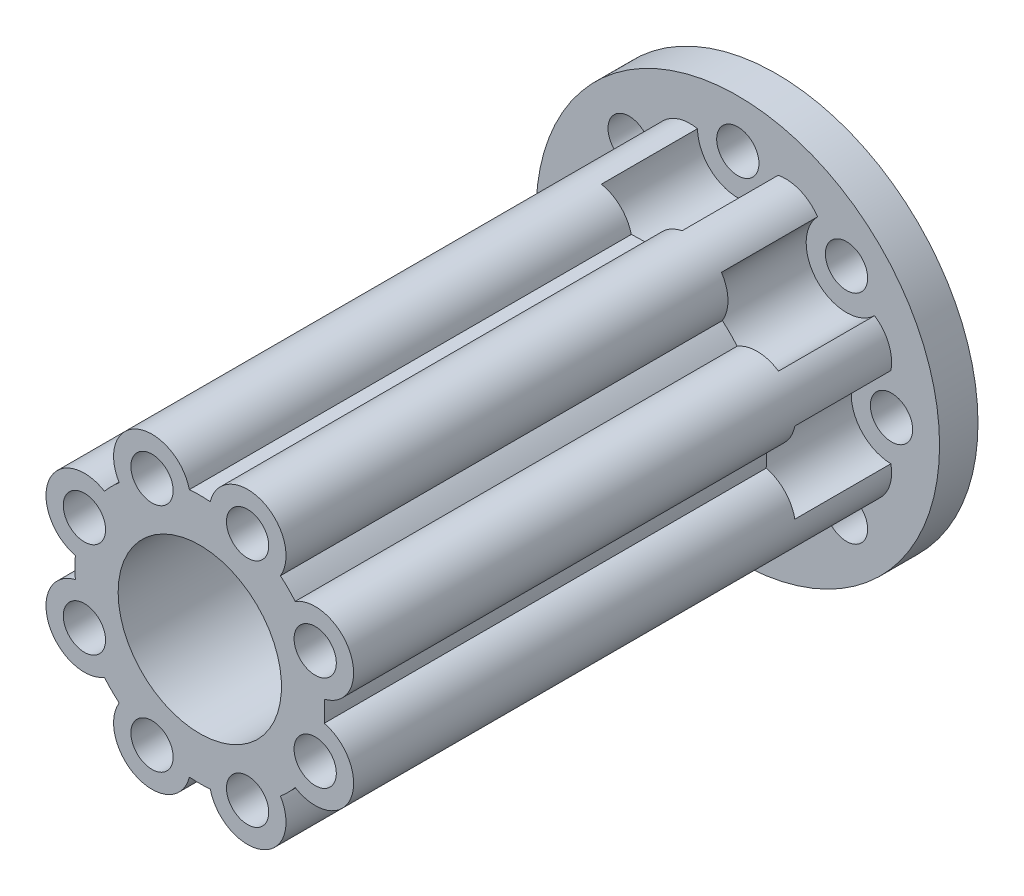
SolidWorks part; units mm, degrees
ref_plane "Alzado" through (0, 0, 0) normal (0, 0, 1) x (1, 0, 0)
ref_plane "Planta" through (0, 0, 0) normal (0, 1, 0) x (1, 0, 0)
ref_plane "Vista lateral" through (0, 0, 0) normal (1, 0, 0) x (0, 0, -1)
sketch "Croquis1" plane through (0, 0, 0) normal (0, 0, 1) x (1, 0, 0)
  circle A0 centre (0, 0) radius 10.5
  circle A1 centre (0, 0) radius 4.25
  dimension "D1" = 21
  dimension "D2" = 8.5
extrude "Saliente-Extruir1" add sketch "Croquis1" along normal blind 2
sketch "Croquis2" plane through (0, 0, 2) normal (0, 0, 1) x (1, 0, 0)
  arc A0 (-6.4347, 4.879) -> (-4.879, 6.4347) centre (-5.6569, 5.6569) ccw construction
  arc A1 (-8, -1.1) -> (-8, 1.1) centre (-8, 0) ccw construction
  arc A2 (-4.879, -6.4347) -> (-6.4347, -4.879) centre (-5.6569, -5.6569) ccw construction
  arc A3 (1.1, -8) -> (-1.1, -8) centre (0, -8) ccw construction
  arc A4 (6.4347, -4.879) -> (4.879, -6.4347) centre (5.6569, -5.6569) ccw construction
  arc A5 (8, 1.1) -> (8, -1.1) centre (8, 0) ccw construction
  arc A6 (4.879, 6.4347) -> (6.4347, 4.879) centre (5.6569, 5.6569) ccw construction
  arc A7 (-1.1, 8) -> (1.1, 8) centre (0, 8) ccw construction
  circle A8 centre (-5.6569, 5.6569) radius 1.1
  circle A9 centre (-8, 0) radius 1.1
  circle A10 centre (-5.6569, -5.6569) radius 1.1
  circle A11 centre (0, -8) radius 1.1
  circle A12 centre (5.6569, -5.6569) radius 1.1
  circle A13 centre (8, 0) radius 1.1
  circle A14 centre (5.6569, 5.6569) radius 1.1
  circle A15 centre (0, 8) radius 1.1
extrude "Cortar-Extruir1" cut sketch "Croquis2" against normal up to next
sketch "Croquis3" plane through (0, 0, 2) normal (0, 0, 1) x (1, 0, 0)
  circle A0 centre (0, 0) radius 4.25
  circle A1 centre (0, 0) radius 6.5
  dimension "D1" = 8.5
  dimension "D2" = 13
extrude "Saliente-Extruir2" add sketch "Croquis3" along normal up to surface (28 mm away)
sketch "Croquis4" plane through (0, 0, 30) normal (0, 0, 1) x (1, 0, 0)
  circle A1 centre (-2.4874, 6.0052) radius 2
  circle A2 centre (2.4874, 6.0052) radius 2
  circle A3 centre (6.0052, 2.4874) radius 2
  circle A4 centre (6.0052, -2.4874) radius 2
  circle A5 centre (2.4874, -6.0052) radius 2
  circle A6 centre (-2.4874, -6.0052) radius 2
  circle A7 centre (-6.0052, -2.4874) radius 2
  circle A8 centre (-6.0052, 2.4874) radius 2
  point P29 (0, 0)
  dimension "D1" = 4
  dimension "D3" = 6.0052
  dimension "D4" = 4.9749
  dimension "D2" = 8
extrude "Saliente-Extruir3" add sketch "Croquis4" against normal up to surface (28 mm away) up to face at (10.5, 0, 2)
sketch "Croquis6" plane through (0, 0, 2) normal (0, 0, 1) x (1, 0, 0)
  circle A0 centre (-5.6569, -5.6569) radius 1.1 construction
  circle A1 centre (0, -8) radius 1.1 construction
  circle A2 centre (5.6569, -5.6569) radius 1.1 construction
  circle A3 centre (8, 0) radius 1.1 construction
  circle A4 centre (5.6569, 5.6569) radius 1.1 construction
  circle A5 centre (0, 8) radius 1.1 construction
  circle A6 centre (-5.6569, 5.6569) radius 1.1 construction
  circle A7 centre (-8, 0) radius 1.1 construction
  circle A8 centre (-5.6569, -5.6569) radius 1.1 construction
  circle A9 centre (0, -8) radius 1.1 construction
  circle A10 centre (5.6569, -5.6569) radius 1.1 construction
  circle A11 centre (8, 0) radius 1.1 construction
  circle A12 centre (5.6569, 5.6569) radius 1.1 construction
  circle A13 centre (0, 8) radius 1.1 construction
  circle A14 centre (-5.6569, 5.6569) radius 1.1 construction
  circle A15 centre (-8, 0) radius 1.1 construction
  circle A16 centre (-5.6569, 5.6569) radius 2.1
  circle A17 centre (0, 8) radius 2.1
  circle A18 centre (5.6569, 5.6569) radius 2.1
  circle A19 centre (8, 0) radius 2.1
  circle A20 centre (5.6569, -5.6569) radius 2.1
  circle A21 centre (0, -8) radius 2.1
  circle A22 centre (-5.6569, -5.6569) radius 2.1
  circle A23 centre (-8, 0) radius 2.1
  dimension "D1" = 1
extrude "Cortar-Extruir2" cut sketch "Croquis6" along normal blind 5
sketch "Croquis7" plane through (0, 0, 0) normal (0, 1, 0) x (1, 0, 0)
  line L2 (0, 0) -> (0, -30) construction
  line L3 (1.1, 0) -> (-1.1, 0) construction
  line L4 (-0.5439, -30) -> (0.5439, -30) construction
  circle A1 centre (0, -12) radius 3.75
  point P8 (0, 0)
  dimension "D2" = 12
  dimension "D1" = 7.5
extrude "Cortar-Extruir3" cut sketch "Croquis7" against normal through all
fillet "Redondeo1" radius 1 1 edges at (-0.3737, -4.2335, 8.2687)
sketch "Croquis8" plane through (0, 0, 30) normal (0, 0, 1) x (1, 0, 0)
  circle A0 centre (-2.4874, 6.0052) radius 1.1
  circle A1 centre (2.4874, 6.0052) radius 1.1
  circle A2 centre (6.0052, 2.4874) radius 1.1
  circle A3 centre (6.0052, -2.4874) radius 1.1
  circle A4 centre (2.4874, -6.0052) radius 1.1
  circle A5 centre (-2.4874, -6.0052) radius 1.1
  circle A6 centre (-6.0052, -2.4874) radius 1.1
  circle A7 centre (-6.0052, 2.4874) radius 1.1
  point P20 (0, 0)
  dimension "D1" = 2.2
  dimension "D2" = 8
extrude "Cortar-Extruir4" cut sketch "Croquis8" against normal blind 10
